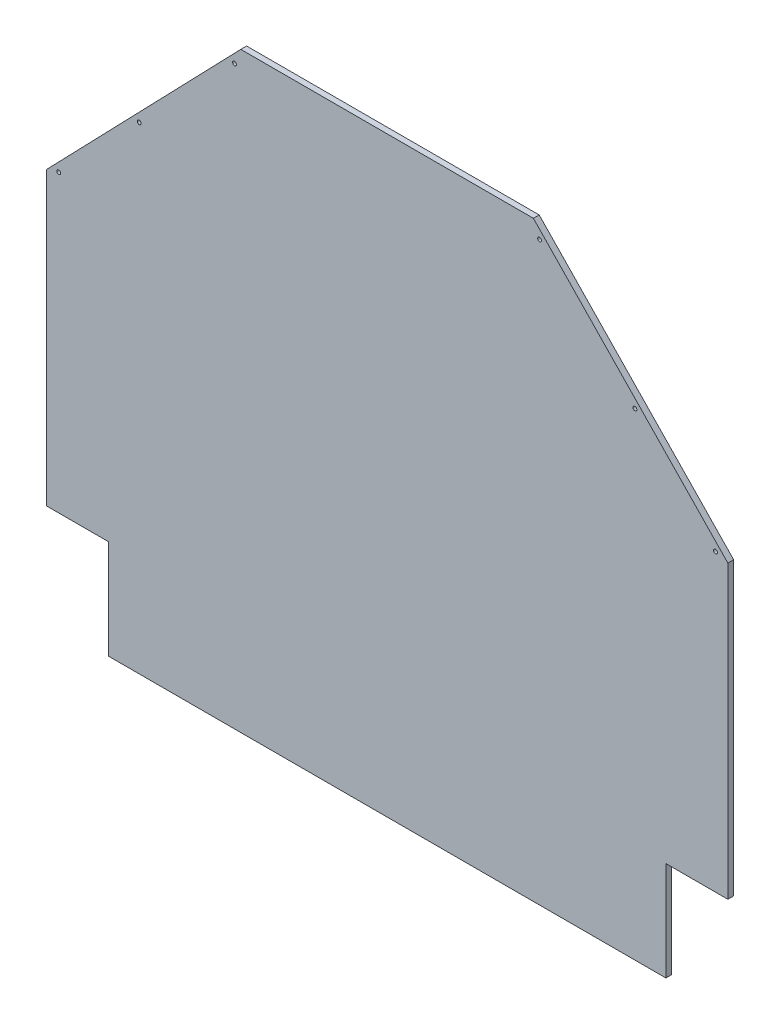
SolidWorks part; units mm, degrees
material "Pine"
ref_plane "Front Plane" through (0, 0, 0) normal (0, 0, 1) x (1, 0, 0)
ref_plane "Top Plane" through (0, 0, 0) normal (0, 1, 0) x (1, 0, 0)
ref_plane "Right Plane" through (0, 0, 0) normal (1, 0, 0) x (0, 0, -1)
sketch "Sketch1" plane through (0, 0, 0) normal (0, 0, 1) x (1, 0, 0)
  line L0 (1068.4674, -524.1043) -> (941.4674, -524.1043)
  line L1 (70.0554, 485.5457) -> (669.8794, 485.5457)
  line L2 (-328.5326, 72.7957) -> (-328.5326, -524.1043)
  line L3 (-201.5326, -727.3043) -> (941.4674, -727.3043)
  line L4 (1068.4674, 72.7957) -> (1068.4674, -524.1043)
  line L5 (-328.5326, -524.1043) -> (-201.5326, -524.1043)
  line L6 (-201.5326, -524.1043) -> (-201.5326, -727.3043)
  line L7 (369.9674, -727.3043) -> (369.9674, -138.7274) construction
  line L8 (-328.5326, -524.1043) -> (-328.5326, 72.7957) construction
  line L9 (-328.5326, 72.7957) -> (70.0554, 485.5457)
  line L10 (941.4674, -524.1043) -> (941.4674, -727.3043)
  line L11 (1068.4674, -524.1043) -> (1068.4674, 72.7957) construction
  line L12 (1068.4674, 72.7957) -> (669.8794, 485.5457)
  line L13 (369.9674, 485.5457) -> (369.9674, -138.7274) construction
  dimension "D2" = 127
  dimension "D3" = 596.9
  dimension "D4" = 127
  dimension "D5" = 596.9
  dimension "D6" = 136
  dimension "D7" = 136
extrude "Boss-Extrude1" add sketch "Sketch1" along normal blind 11.9062
hole_wizard "5/16 (0.3125) Diameter Hole1" positions "Sketch2" profile "Sketch3" hole size "5/16" standard "ANSI Inch" end condition through all
sketch "Sketch2" plane through (0, 0, 11.9062) normal (0, 0, 1) x (1, 0, 0)
  line L0 (70.0554, 485.5457) -> (-328.5326, 72.7957) construction
  line L1 (-328.5326, 72.7957) -> (-328.5326, -524.1043) construction
  line L2 (1068.4674, 72.7957) -> (669.8794, 485.5457) construction
  point P0 (-303.1326, 80.8158)
  point P2 (-138.0326, 251.7819)
  point P4 (57.3554, 454.1121)
  point P6 (682.5794, 454.1121)
  point P8 (877.9674, 251.7819)
  point P10 (1043.0674, 80.8158)
  dimension "D1" = 12.7
  dimension "D2" = 12.7
  dimension "D3" = 12.7
  dimension "D4" = 25.4
  dimension "D5" = 12.7
  dimension "D6" = 12.7
  dimension "D7" = 12.7
  dimension "D8" = 12.7
  dimension "D9" = 190.5
sketch "Sketch3" plane through (-303.1326, 80.8158, 11.9062) normal (1, 0, 0) x (0, -1, 0)
  line L0 (0, 0) -> (0, 11.9062)
  line L1 (0, 11.9062) -> (3.9687, 11.9062)
  line L2 (3.9687, 11.9062) -> (3.9687, 0)
  line L5 (3.9687, 0) -> (0, 0)
  line L11 (0, -6.35) -> (0, 107.95) construction
  dimension "Thru Hole Dia." = 7.9375
  dimension "Thru Hole Depth" = 11.9062
